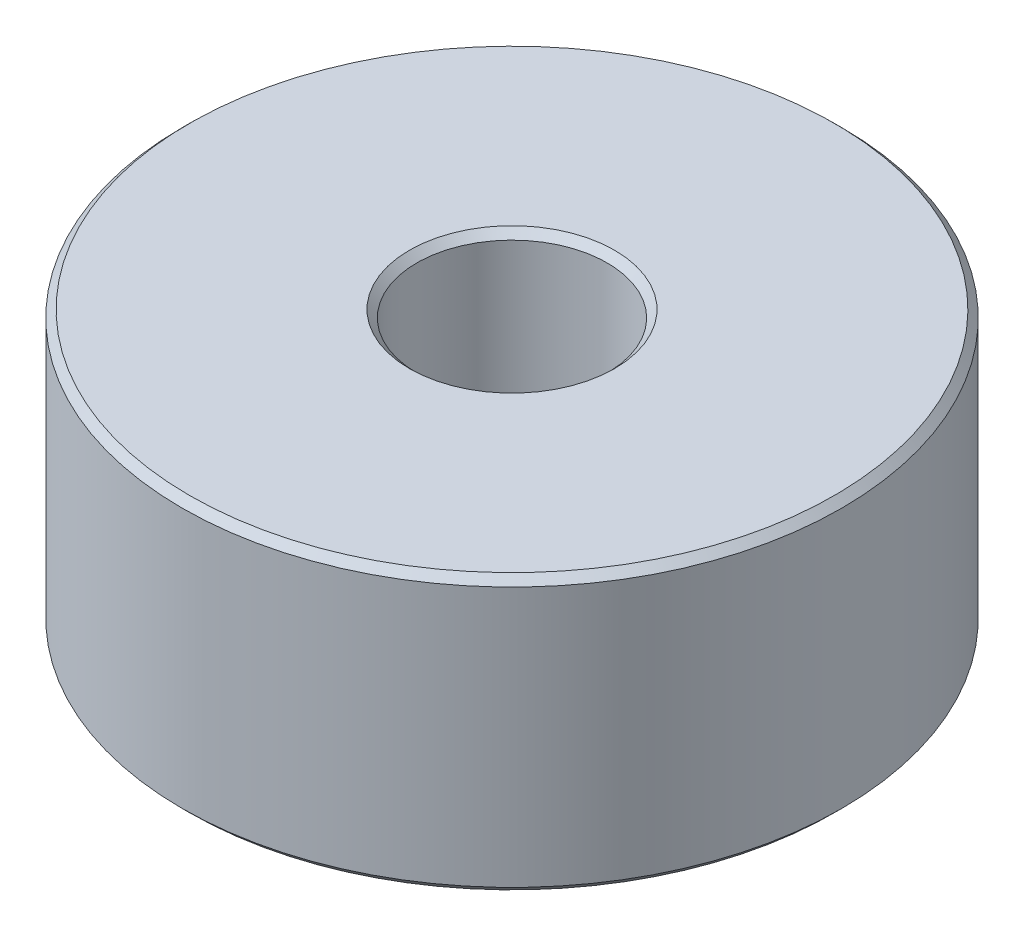
SolidWorks part; units mm, degrees
ref_plane "Front Plane" through (0, 0, 0) normal (0, 0, 1) x (1, 0, 0)
ref_plane "Top Plane" through (0, 0, 0) normal (0, 1, 0) x (1, 0, 0)
ref_plane "Right Plane" through (0, 0, 0) normal (1, 0, 0) x (0, 0, -1)
sketch "Sketch1" plane through (0, 0, 0) normal (0, 1, 0) x (1, 0, 0)
  circle A0 centre (0, 0) radius 9
  circle A1 centre (0, 0) radius 2.6
  dimension "D1" = 18
  dimension "D2" = 5.2
extrude "Boss-Extrude1" add sketch "Sketch1" along normal blind 7.5
chamfer "Chamfer1" distance 0.2 angle 45 4 edges at (0, 0, 2.6) (0, 0, 9) (0, 7.5, 2.6) (0, 7.5, 9)
